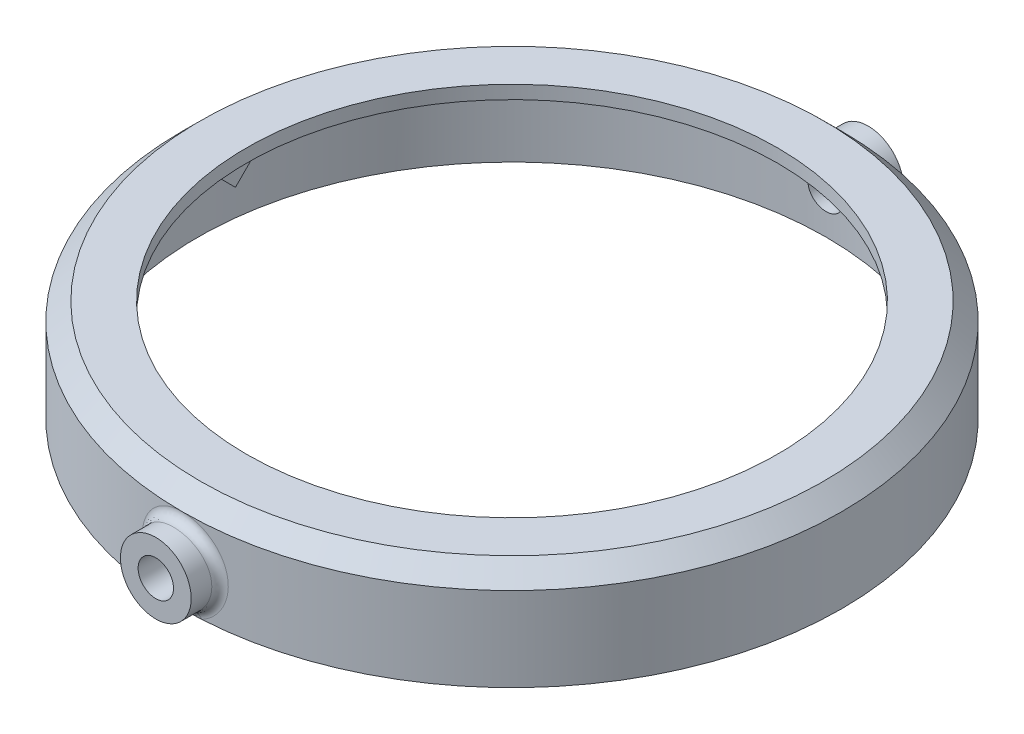
SolidWorks part; units mm, degrees
ref_plane "Front Plane" through (0, 0, 0) normal (0, 0, 1) x (1, 0, 0)
ref_plane "Top Plane" through (0, 0, 0) normal (0, 1, 0) x (1, 0, 0)
ref_plane "Right Plane" through (0, 0, 0) normal (1, 0, 0) x (0, 0, -1)
sketch "Sketch1" plane through (0, 0, 0) normal (0, 1, 0) x (1, 0, 0)
  line L0 (0, 0) -> (0, 13.7725) construction
  line L1 (0, 0) -> (-10.9504, 0) construction
  circle A0 centre (0, 0) radius 35.5
  circle A1 centre (0, 0) radius 35 construction
  circle A2 centre (0, 0) radius 37.25
  circle A3 centre (0, 0) radius 30
  dimension "D1" = 71
  dimension "D2" = 70
  dimension "D3" = 1.75
  dimension "D4" = 60
extrude "Boss-Extrude1" add sketch "Sketch1" against normal blind 10 contours A2 A0 region at (-36.1964, 0, 0)
extrude "Boss-Extrude2" add sketch "Sketch1<2>" along normal blind 1.5 contours A0 | A2 A0 region at (-34.4959, 0, 0) region at (-36.1964, 0, 0)
sketch "Sketch1<2>" plane through (0, 0, 0) normal (0, 1, 0) x (1, 0, 0) same geometry as "Sketch1"
chamfer "Chamfer1" distance 1.5 angle 45 1 edges at (0, 0, 35.5)
chamfer "Chamfer2" distance 2 angle 45 1 edges at (0, 1.5, 37.25)
ref_plane "Plane1" through (0, 0, 37.25) normal (0, 0, 1) x (1, 0, 0)
sketch "Sketch2" plane through (0, 0, 37.25) normal (0, 0, 1) x (1, 0, 0)
  line L0 (0, -0.5) -> (0, -10) construction
  line L1 (-37.25, -0.5) -> (37.25, -0.5) construction
  line L2 (-37.25, -10) -> (37.25, -10) construction
  circle A0 centre (0, -5.5) radius 2
  circle A1 centre (0, -5.5) radius 4
  dimension "D1" = 4
  dimension "D2" = 2
  dimension "D3" = 5
extrude "Cut-Extrude1" cut sketch "Sketch2" against normal blind 10 contours L0 A0 | A0 L0 region at (0.8488, -5.5, 37.25) region at (-0.8488, -5.5, 37.25)
extrude "Boss-Extrude4" add sketch "Sketch2<3>" along normal blind 3 and the other way blind 1 contours A1 L0 A0 | L0 A1 A0 region at (2.7652, -2.7348, 37.25) region at (-0.0894, -2.5, 37.25)
sketch "Sketch2<3>" plane through (0, 0, 37.25) normal (0, 0, 1) x (1, 0, 0) same geometry as "Sketch2"
mirror "Mirror1" about plane through (0, 0, 0) normal (0, 0, 1) of "Boss-Extrude4", "Cut-Extrude1"
ref_plane "Plane2" through (37.25, 0, 0) normal (1, 0, 0) x (0, 0, -1)
sketch "tirangle" plane through (37.25, 0, 0) normal (1, 0, 0) x (0, 0, -1)
  line L0 (0, -0.5) -> (0, -13.8889) construction
  line L2 (2.5, -0.5) -> (-2.5, -0.5)
  line L6 (-2.5, -0.5) -> (0, -3)
  line L7 (-37.25, -0.5) -> (37.25, -0.5) construction
  line L8 (0, -3) -> (2.5, -0.5)
  dimension "D1" = 45
  dimension "D2" = 5
extrude "Boss-Extrude6" add sketch "tirangle" against normal blind 5 from offset 1 offset against normal yes
mirror "Mirror2" about plane through (0, 0, 0) normal (1, 0, 0) of "Boss-Extrude6"
fillet "Fillet1" radius 1 2 edges at (3.8988, -4.6059, -37.0454) (-0.8941, -1.6012, 37.2393)
